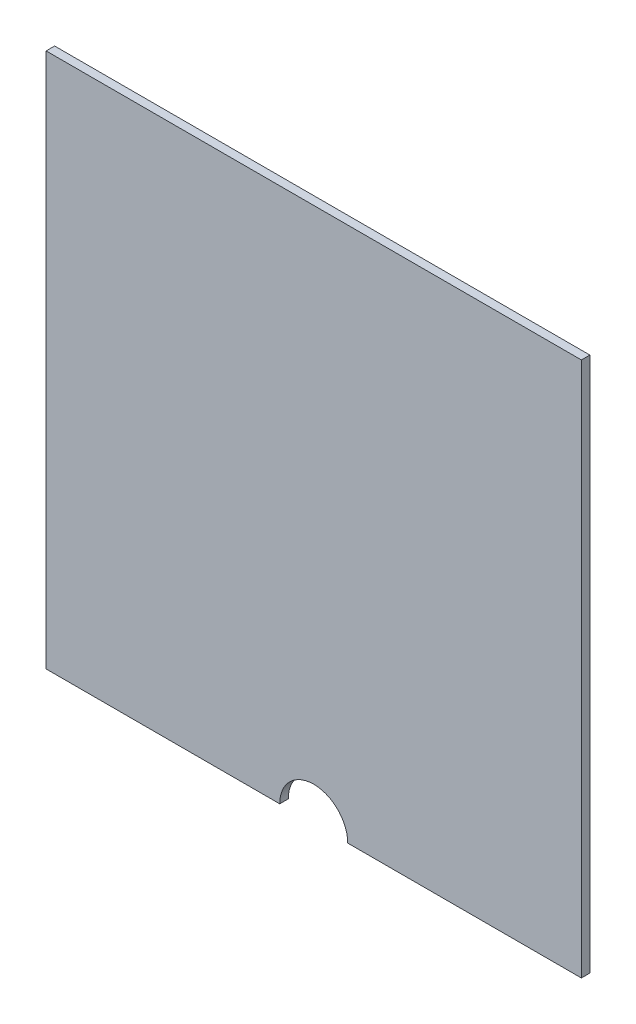
SolidWorks part; units mm, degrees
material "PVC Rigid"
ref_plane "Front Plane" through (0, 0, 0) normal (0, 0, 1) x (1, 0, 0)
ref_plane "Top Plane" through (0, 0, 0) normal (0, 1, 0) x (1, 0, 0)
ref_plane "Right Plane" through (0, 0, 0) normal (1, 0, 0) x (0, 0, -1)
sketch "Sketch1" plane through (0, 0, 0) normal (0, 0, 1) x (1, 0, 0)
  line L1 (0, 0) -> (199.873, 0)
  line L2 (0, 0) -> (0, 199.873)
  line L3 (0, 199.873) -> (199.873, 199.873)
  line L4 (199.873, 0) -> (199.873, 199.873)
  dimension "D1" = 199.873
extrude "Boss-Extrude1" add sketch "Sketch1" along normal blind 3.175
sketch "Sketch3" plane through (0, 0, 3.175) normal (0, 0, 1) x (1, 0, 0)
  line L0 (99.9365, 199.873) -> (99.9365, 0) construction
  line L1 (199.873, 199.873) -> (0, 199.873) construction
  line L2 (0, 0) -> (199.873, 0) construction
  line L3 (87.2365, 0) -> (112.6365, 0)
  arc A0 (112.6365, 0) -> (87.2365, 0) centre (99.9365, 0) ccw
  dimension "D1" = 25.4
extrude "Cut-Extrude3" cut sketch "Sketch3" against normal blind 3.175
sketch "Sketch4" plane through (0, 0, 3.175) normal (0, 0, 1) x (1, 0, 0)
  line L0 (2.54, 2.54) -> (199.873, 2.54) construction
  line L1 (199.873, 0) -> (199.873, 199.873) construction
  line L3 (0, 0) -> (2.54, 0) construction
  line L4 (0, 0) -> (0, 2.54) construction
  line L5 (0, 2.54) -> (2.54, 2.54) construction
  line L6 (2.54, 0) -> (2.54, 2.54) construction
  text T0 "SP_BIT" font "Consolas" height 3.5
  dimension "D1" = 2.54
extrude "Cut-Extrude4" [suppressed] cut sketch "Sketch4" against normal blind 1.5875
